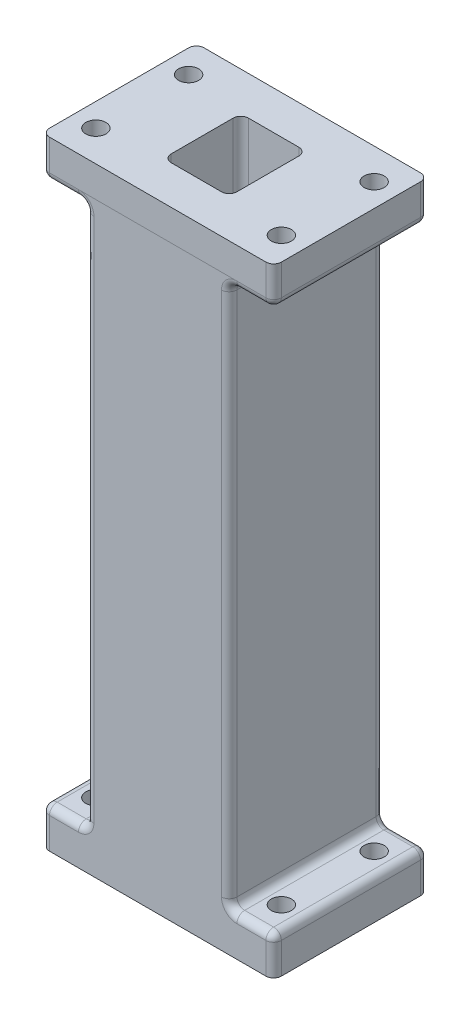
SolidWorks part; units mm, degrees
material "ABS"
ref_plane "Front Plane" through (0, 0, 0) normal (0, 0, 1) x (1, 0, 0)
ref_plane "Top Plane" through (0, 0, 0) normal (0, 1, 0) x (1, 0, 0)
ref_plane "Right Plane" through (0, 0, 0) normal (1, 0, 0) x (0, 0, -1)
sketch "Sketch1" plane through (0, 0, 0) normal (0, 1, 0) x (1, 0, 0)
  line L0 (-40, 0) -> (40, 0) construction
  line L1 (0, -40) -> (0, 40) construction
  line L2 (12, -6) -> (12, 6) construction
  line L3 (-12, -6) -> (12, -6) construction
  line L4 (-12, -6) -> (-12, 6) construction
  line L5 (-12, 6) -> (12, 6) construction
  line L7 (-15, -10) -> (15, -10)
  line L8 (-15, -10) -> (-15, 10)
  line L9 (-15, 10) -> (15, 10)
  line L10 (15, -10) -> (15, 10)
  line L11 (-15, -10) -> (15, 10) construction
  line L12 (-15, 10) -> (15, -10) construction
  circle A0 centre (0, 0) radius 8 construction
  circle A13 centre (-12, 6) radius 1.3
  circle A14 centre (12, 6) radius 1.3
  circle A15 centre (12, -6) radius 1.3
  circle A16 centre (-12, -6) radius 1.3
  circle A17 centre (0, 8) radius 1 construction
  circle A18 centre (5.6569, 5.6569) radius 1 construction
  circle A19 centre (8, 0) radius 1 construction
  circle A20 centre (5.6569, -5.6569) radius 1 construction
  circle A21 centre (0, -8) radius 1 construction
  circle A22 centre (-5.6569, -5.6569) radius 1 construction
  circle A23 centre (-8, 0) radius 1 construction
  circle A24 centre (-5.6569, 5.6569) radius 1 construction
  point P3 (0, 0)
  point P6 (0, 0)
  point P26 (0, 0)
  point P28 (12, 0)
  point P31 (0, -6)
  point P38 (0, 0)
  dimension "D1" = 16
  dimension "D4" = 2.6
  dimension "D5" = 2
  dimension "D2" = 12
  dimension "D3" = 24
  dimension "D7" = 20
  dimension "D8" = 30
  dimension "D6" = 8
extrude "Boss-Extrude1" add sketch "Sketch1" along normal blind 5
sketch "Sketch2" plane through (0, 5, 0) normal (0, 1, 0) x (1, 0, 0)
  line L0 (15, 10) -> (-15, 10) construction
  line L1 (-9.25, -10) -> (9.25, -10)
  line L2 (-9.25, -10) -> (-9.25, 10)
  line L3 (-9.25, 10) -> (9.25, 10)
  line L4 (9.25, -10) -> (9.25, 10)
  line L5 (-9.25, -10) -> (9.25, 10) construction
  line L6 (-9.25, 10) -> (9.25, -10) construction
  point P0 (0, 0)
  dimension "D1" = 18.5
extrude "Boss-Extrude2" add sketch "Sketch2" along normal blind 70
ref_axis "Axis1" through (9.25, 40, 10) along (-1, 0, 0)
ref_plane "Plane1" through (0, 40, 0) normal (0, 1, 0) x (1, 0, 0)
mirror "Mirror1" about plane through (0, 40, 0) normal (0, 1, 0) of "Boss-Extrude1"
ref_plane "Plane2" through (0, 40, 0) normal (0, 1, 0) x (1, 0, 0)
sketch "Sketch8" plane through (0, 40, 0) normal (0, 1, 0) x (1, 0, 0)
  line L0 (-9.25, 10) -> (-9.25, -10) construction
  line L1 (9.25, -10) -> (9.25, 10) construction
  line L2 (-9.25, 10) -> (-9.25, -10) construction
  line L3 (9.25, -10) -> (9.25, 10) construction
  line L4 (-9.25, 5.5) -> (-4.75, 5.5)
  line L5 (-4.75, 5.5) -> (-4.75, -5.5)
  line L6 (-4.75, -5.5) -> (-9.25, -5.5)
  line L8 (0, 10) -> (0, -10) construction
  line L9 (15, 10) -> (-15, 10) construction
  line L10 (-15, -10) -> (15, -10) construction
  line L11 (-9.25, 5.5) -> (-9.25, -5.5)
  line L12 (4.75, -5.5) -> (9.25, -5.5)
  line L13 (9.25, 5.5) -> (9.25, -5.5)
  line L14 (9.25, 5.5) -> (4.75, 5.5)
  line L15 (4.75, 5.5) -> (4.75, -5.5)
  dimension "D1" = 4.5
  dimension "D2" = 4.5
  dimension "D3" = 4.5
ref_point "Point9"
ref_axis "Axis2" through (0, 80, 0) along (0, 1, 0)
sketch "Sketch9" plane through (0, 0, 10) normal (0, 0, 1) x (1, 0, 0)
  line L0 (-15, 78) -> (15, 78) construction
  line L3 (-15, 80) -> (15, 80) construction
  line L4 (15, 75) -> (15, 80) construction
  line L5 (-15, 75) -> (-15, 80) construction
  point P11 (0, 78)
  dimension "D1" = 2
ref_point "Point4"
sketch "Sketch10" plane through (15, 0, 0) normal (1, 0, 0) x (0, 0, -1)
  line L0 (-10, 78) -> (10, 78) construction
  line L2 (-10, 80) -> (10, 80) construction
  line L3 (10, 75) -> (10, 80) construction
  line L4 (-10, 75) -> (-10, 80) construction
  point P8 (0, 78)
  dimension "D1" = 2
ref_point "Point6"
fillet "Fillet1" radius 1 28 edges at (12.125, 5, -10) (12.125, 5, 10) (-12.125, 5, -10) (-12.125, 5, 10) (-9.25, 75, 0) (9.25, 75, 0) (12.125, 75, 10) (15, 75, 0) (12.125, 75, -10) (9.25, 40, -10) (15, 5, 0) (9.25, 40, 10) (9.25, 5, 0) (-15, 5, 0) (-9.25, 5, 0) (-9.25, 40, 10) (-9.25, 40, -10) (-12.125, 75, -10) (-15, 75, 0) (-12.125, 75, 10) (15, 2.5, -10) (15, 2.5, 10) (-15, 2.5, 10) (-15, 2.5, -10) (-15, 77.5, -10) (-15, 77.5, 10) (15, 77.5, -10) (15, 77.5, 10)
sketch "Sketch11" plane through (0, 0, 10) normal (0, 0, 1) x (1, 0, 0)
  line L1 (-14, 80) -> (14, 80)
  line L2 (-14, 80) -> (-14, 76)
  line L3 (-14, 76) -> (14, 76)
  line L4 (14, 80) -> (14, 76)
split line "Split Line1"
sketch "Sketch12" plane through (0, 80, 0) normal (0, 1, 0) x (1, 0, 0)
  line L0 (14, 10) -> (-14, 10) construction
  line L1 (-9.25, -10) -> (9.25, -10) construction
  line L2 (-9.25, -10) -> (-9.25, 10) construction
  line L3 (-9.25, 10) -> (9.25, 10) construction
  line L4 (9.25, -10) -> (9.25, 10) construction
  line L5 (-9.25, -10) -> (9.25, 10) construction
  line L6 (-9.25, 10) -> (9.25, -10) construction
  line L7 (-4.25, -5) -> (-4.25, 5)
  line L8 (-4.25, 5) -> (4.25, 5)
  line L9 (4.25, -5) -> (4.25, 5)
  line L10 (-4.25, -5) -> (4.25, -5)
  point P0 (0, 0)
  dimension "D1" = 18.5
  dimension "D2" = 5
extrude "Cut-Extrude1" cut sketch "Sketch12" against normal through all
fillet "Fillet2" radius 1 4 edges at (4.25, 40, 5) (-4.25, 40, 5) (4.25, 40, -5) (-4.25, 40, -5)
